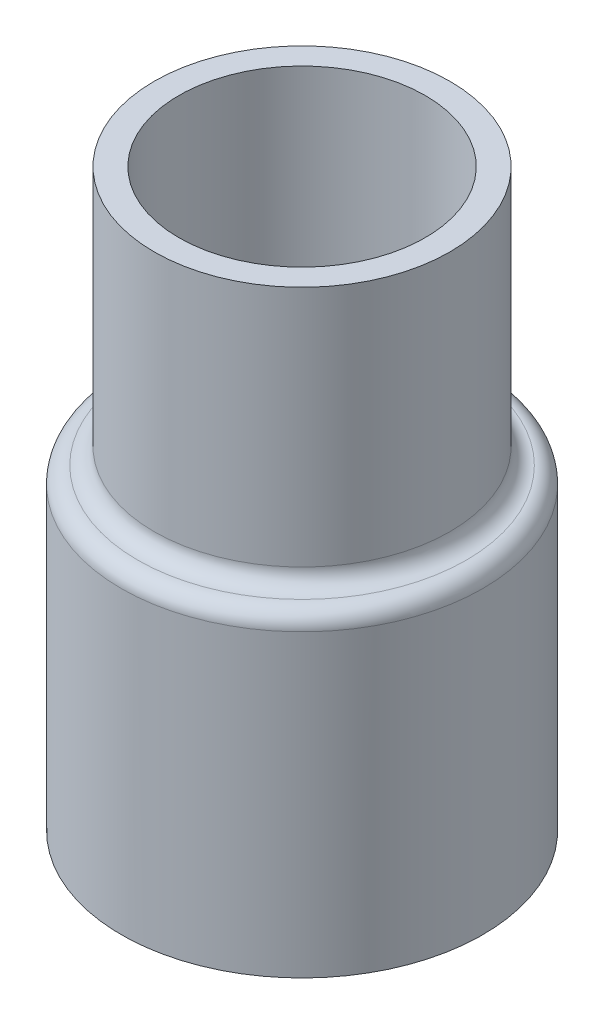
SolidWorks part; units mm, degrees
ref_plane "Front Plane" through (0, 0, 0) normal (0, 0, 1) x (1, 0, 0)
ref_plane "Top Plane" through (0, 0, 0) normal (0, 1, 0) x (1, 0, 0)
ref_plane "Right Plane" through (0, 0, 0) normal (1, 0, 0) x (0, 0, -1)
sketch "Sketch1" plane through (0, 0, 0) normal (1, 0, 0) x (0, 0, -1)
  line L0 (0, -17.5) -> (0, 17.5) construction
  line L1 (7.5, 17.5) -> (9, 17.5)
  line L2 (9, 17.5) -> (9, 1.75)
  line L3 (9, 1.75) -> (11, 1.75)
  line L4 (11, 1.75) -> (11, -17.5)
  line L5 (11, -17.5) -> (9.5, -17.5)
  line L6 (9.5, -17.5) -> (9.5, -1.75)
  line L7 (9.5, -1.75) -> (7.5, -1.75)
  line L8 (7.5, -1.75) -> (7.5, 17.5)
  point P4 (0, 0)
  dimension "D1" = 35
  dimension "D2" = 9
  dimension "D3" = 15
  dimension "D4" = 22
  dimension "D5" = 3.5
revolve "Revolve1" add sketch "Sketch1" angle 360 about L0
fillet "Fillet1" radius 1 2 edges at (0, 1.75, -9) (0, 1.75, -11)
